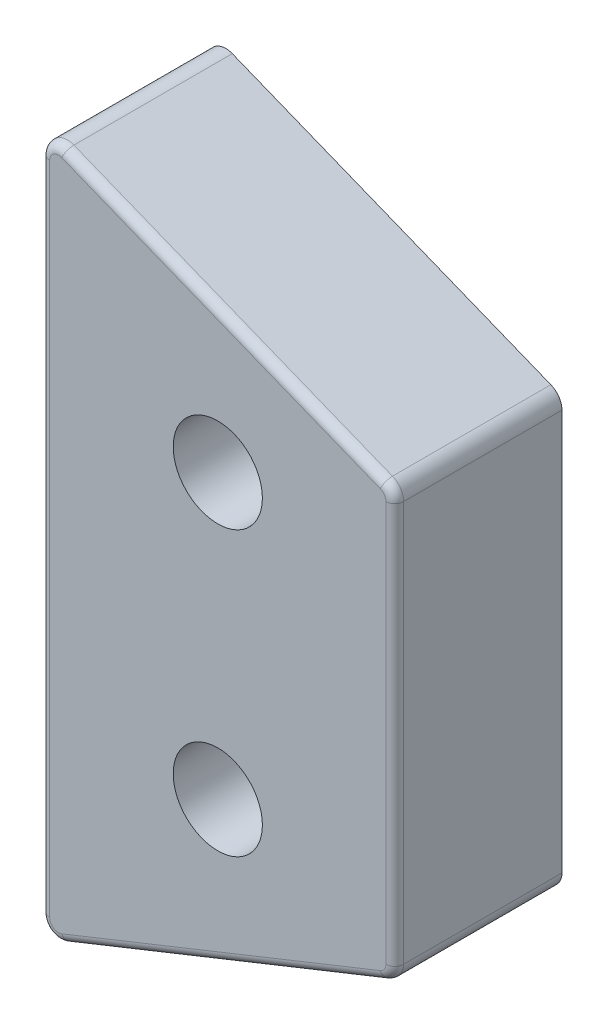
SolidWorks part; units mm, degrees
ref_plane "Front Plane" through (0, 0, 0) normal (0, 0, 1) x (1, 0, 0)
ref_plane "Top Plane" through (0, 0, 0) normal (0, 1, 0) x (1, 0, 0)
ref_plane "Right Plane" through (0, 0, 0) normal (1, 0, 0) x (0, 0, -1)
sketch "Sketch1" plane through (0, 0, 0) normal (0, 0, 1) x (1, 0, 0)
  line L0 (0, 0) -> (15.875, -6.35)
  line L1 (15.875, -6.35) -> (15.875, -25.4)
  line L2 (15.875, -25.4) -> (0, -31.75)
  line L3 (0, -31.75) -> (0, 0)
  line L4 (7.9375, -3.175) -> (7.9375, -9.525) construction
  line L5 (7.9375, -9.525) -> (7.9375, -22.225) construction
  line L6 (7.9375, -22.225) -> (7.9375, -28.575) construction
  circle A0 centre (7.9375, -22.225) radius 2
  circle A1 centre (7.9375, -9.525) radius 2
  dimension "D4" = 4
  dimension "D1" = 31.75
  dimension "D2" = 19.05
  dimension "D3" = 15.875
  dimension "D5" = 9.525
extrude "Boss-Extrude1" add sketch "Sketch1" along normal blind 7.5
fillet "Fillet1" radius 0.7937 4 edges at (0, -31.75, 3.75) (15.875, -25.4, 3.75) (15.875, -6.35, 3.75) (0, 0, 3.75)
sketch "Sketch2" plane through (0, 0, 7.5) normal (0, 0, 1) x (1, 0, 0)
  line L0 (14.6875, -22.225) -> (14.6875, -25.875)
  line L1 (1.0885, -31.3146) -> (15.376, -25.5996) construction
  line L2 (1.1875, -22.225) -> (1.1875, -31.275)
  line L3 (1.1875, -31.275) -> (14.6875, -25.875)
  arc A0 (14.6875, -22.225) -> (1.1875, -22.225) centre (7.9375, -22.225) ccw
  dimension "D1" = 13.5
extrude "Cut-Extrude1" cut sketch "Sketch2" against normal blind 4.25
fillet "Fillet2" radius 0.3969 8 edges at (15.7385, -6.4424, 0) (15.875, -15.875, 0) (15.7385, -25.3076, 0) (8.2323, -28.4571, 0) (0.3488, -31.2349, 0) (0, -15.875, 0) (0.3488, -0.5151, 0) (8.2323, -3.2929, 0)
mirror "Mirror1" about plane through (0, 0, 0) normal (0, 0, -1) of bodies 102
delete or keep bodies "Body-Delete/Keep 1" type delete bodies bodies 102
